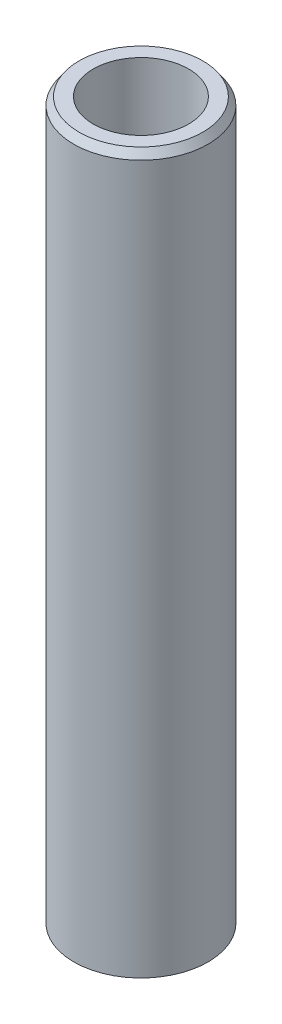
SolidWorks part; units mm, degrees
ref_plane "Front Plane" through (0, 0, 0) normal (0, 0, 1) x (1, 0, 0)
ref_plane "Top Plane" through (0, 0, 0) normal (0, 1, 0) x (1, 0, 0)
ref_plane "Right Plane" through (0, 0, 0) normal (1, 0, 0) x (0, 0, -1)
sketch "Sketch1" plane through (0, 0, 0) normal (0, 1, 0) x (1, 0, 0)
  circle A0 centre (0, 0) radius 50
  dimension "SHAFT_OD" = 100
extrude "Boss-Extrude1" add sketch "Sketch1" along normal blind 536.8129
sketch "Sketch2" plane through (0, 0, 0) normal (0, 1, 0) x (1, 0, 0)
  circle A0 centre (0, 0) radius 35.5339
  dimension "BORE_D" = 71.0677
extrude "Cut-Extrude1" cut sketch "Sketch2" along normal through all
chamfer "Chamfer1" distance 5.7714 angle 34.46 2 edges at (0, 536.8129, 50) (0, 0, 50) first distance on face at (0, 536.8129, 50) first distance on face at (0, 0, 35.5339)
